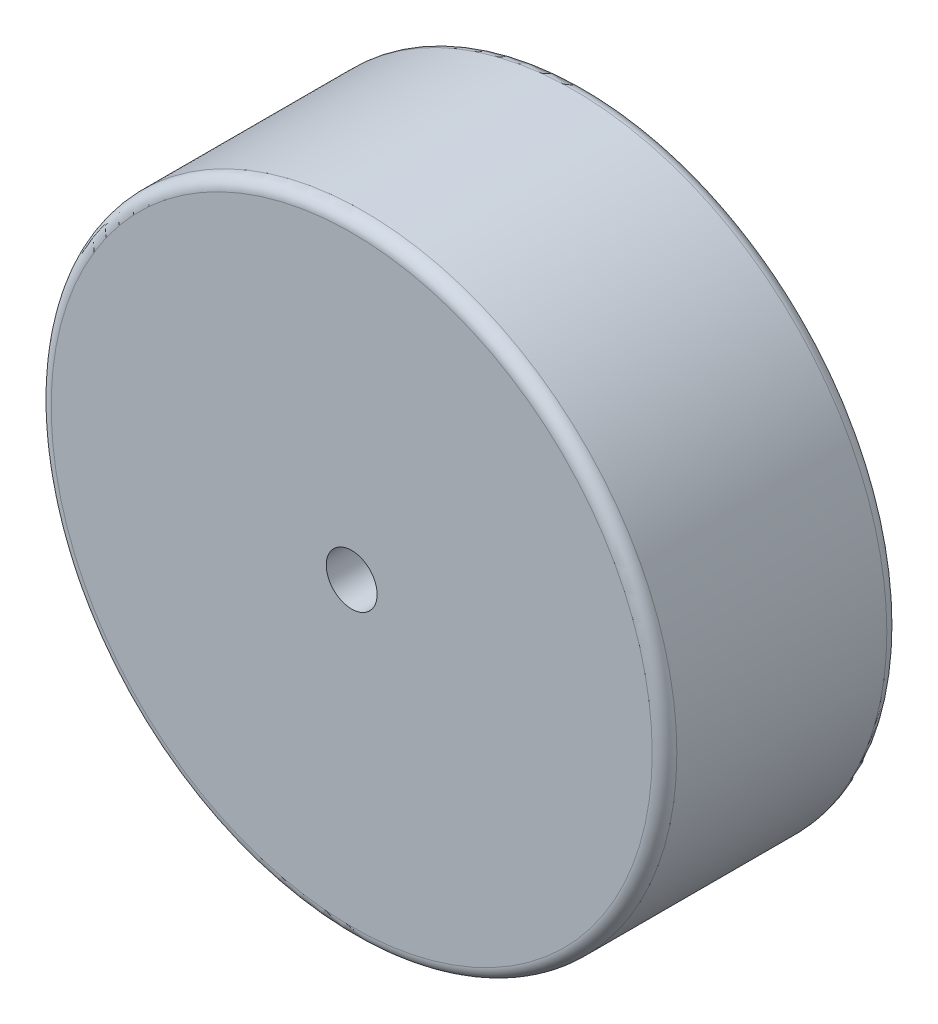
SolidWorks part; units mm, degrees
ref_plane "Front Plane" through (0, 0, 0) normal (0, 0, 1) x (1, 0, 0)
ref_plane "Top Plane" through (0, 0, 0) normal (0, 1, 0) x (1, 0, 0)
ref_plane "Right Plane" through (0, 0, 0) normal (1, 0, 0) x (0, 0, -1)
sketch "body sketch" plane through (0, 0, 0) normal (0, 0, 1) x (1, 0, 0)
  circle A0 centre (0, 0) radius 25.4
  dimension "D1" = 50.8
extrude "wheel body" add sketch "body sketch" along normal mid plane 19.05 contours A0
sketch "hole sketch" plane through (0, 0, 9.525) normal (0, 0, 1) x (1, 0, 0)
  circle A0 centre (0, 0) radius 2.065
  dimension "D1" = 4.13
fillet "fillet wheel" radius 1 2 edges at (25.4, 0, -9.525) (25.4, 0, 9.525)
extrude "hole shaft" cut sketch "hole sketch" against normal up to surface (19.05 mm away) contours A0 up to face at (24.4, 0, -9.525)
